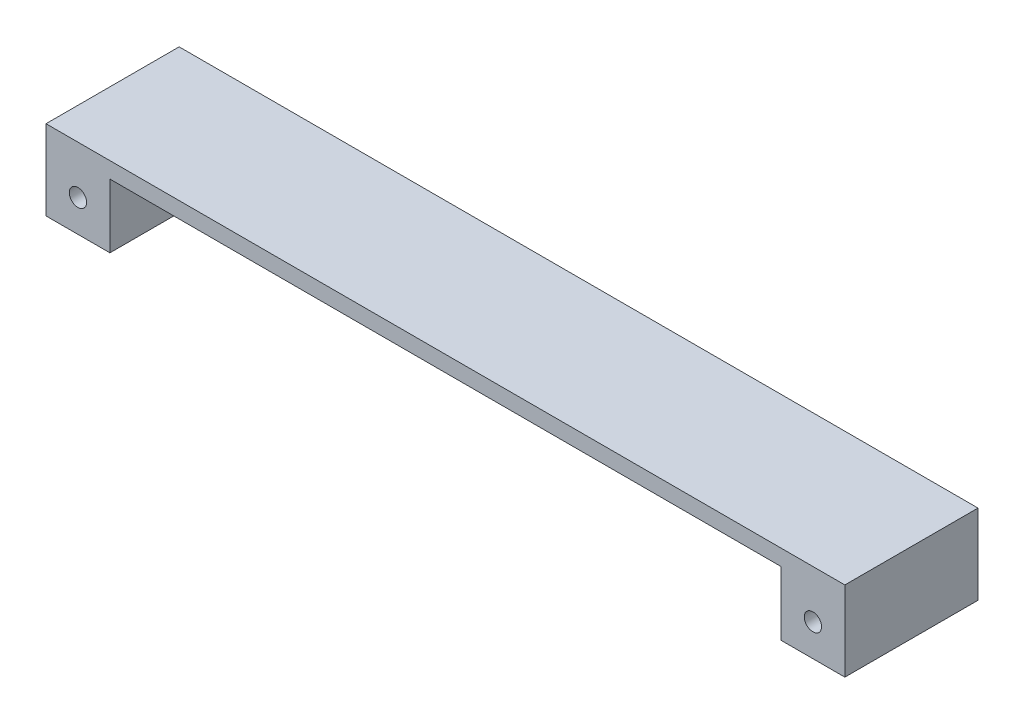
SolidWorks part; units mm, degrees
ref_plane "Front Plane" through (0, 0, 0) normal (0, 0, 1) x (1, 0, 0)
ref_plane "Top Plane" through (0, 0, 0) normal (0, 1, 0) x (1, 0, 0)
ref_plane "Right Plane" through (0, 0, 0) normal (1, 0, 0) x (0, 0, -1)
sketch "Sketch1" plane through (0, 0, 0) normal (0, 1, 0) x (1, 0, 0)
  line L1 (0, 0) -> (150, 0)
  line L2 (0, 0) -> (0, 25)
  line L3 (0, 25) -> (150, 25)
  line L4 (150, 0) -> (150, 25)
  dimension "D1" = 150
  dimension "D2" = 25
extrude "Boss-Extrude1" add sketch "Sketch1" along normal blind 3
sketch "Sketch2" plane through (0, 0, 0) normal (0, -1, 0) x (1, 0, 0)
  line L0 (75, 0) -> (75, -25) construction
  line L1 (0, 0) -> (12, 0)
  line L2 (0, 0) -> (0, -25)
  line L3 (0, -25) -> (12, -25)
  line L4 (12, 0) -> (12, -25)
  line L5 (0, 0) -> (150, 0) construction
  line L6 (150, -25) -> (0, -25) construction
  line L7 (150, -25) -> (138, -25)
  line L8 (138, 0) -> (138, -25)
  line L9 (150, 0) -> (138, 0)
  line L10 (150, 0) -> (150, -25)
  line L11 (0, -12.5) -> (150, -12.5) construction
  line L12 (0, -25) -> (0, 0) construction
  line L13 (150, 0) -> (150, -25) construction
  dimension "D1" = 25
  dimension "D2" = 12
extrude "Boss-Extrude2" add sketch "Sketch2" along normal blind 12
sketch "Sketch4" plane through (0, 0, 0) normal (0, 0, 1) x (1, 0, 0)
  line L0 (12, -12) -> (12, 0) construction
  line L1 (12, -12) -> (0, -12) construction
  line L2 (75, 3) -> (75, 0) construction
  line L3 (0, 3) -> (150, 3) construction
  line L4 (12, 0) -> (138, 0) construction
  circle A0 centre (6, -6) radius 1.625
  circle A1 centre (144, -6) radius 1.625
  dimension "D1" = 3.25
  dimension "D2" = 6
  dimension "D3" = 6
extrude "Cut-Extrude1" cut sketch "Sketch4" against normal through all
